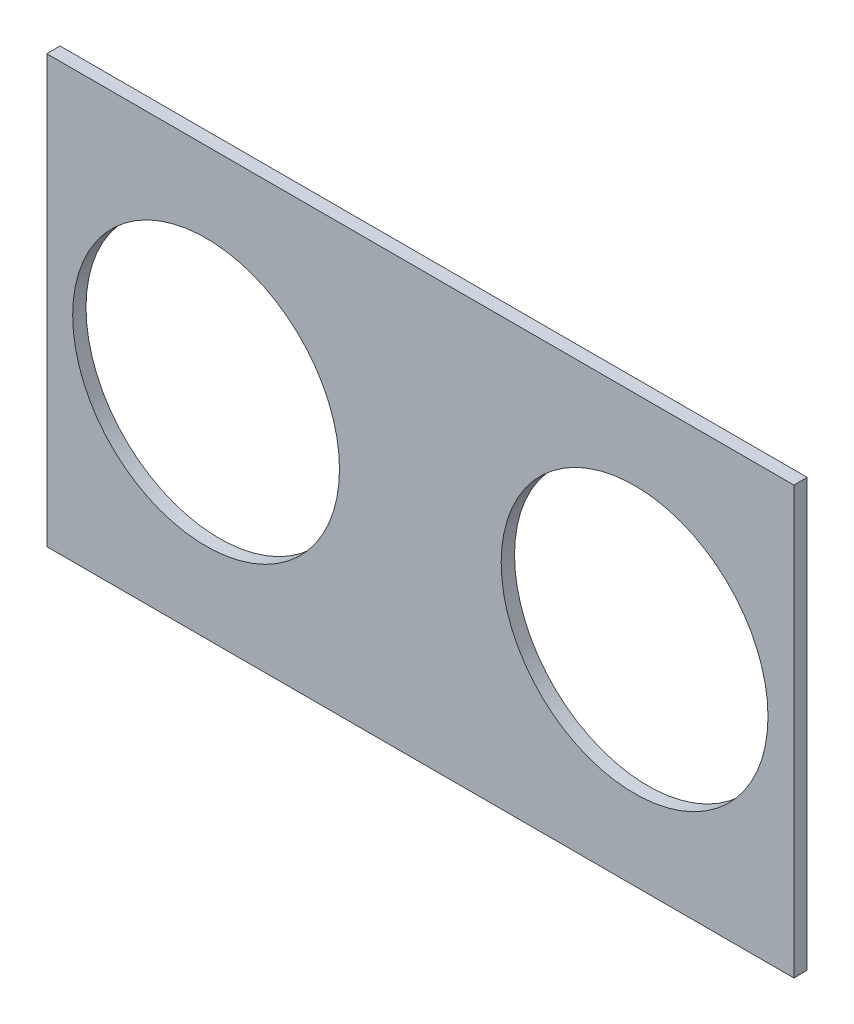
SolidWorks part; units mm, degrees
material "ABS PC"
ref_plane "Front Plane" through (0, 0, 0) normal (0, 0, 1) x (1, 0, 0)
ref_plane "Top Plane" through (0, 0, 0) normal (0, 1, 0) x (1, 0, 0)
ref_plane "Right Plane" through (0, 0, 0) normal (1, 0, 0) x (0, 0, -1)
sketch "Sketch1" plane through (0, 0, 0) normal (0, 0, 1) x (1, 0, 0)
  line L1 (-18.9548, 25.4) -> (69.9452, 25.4)
  line L2 (-18.9548, 25.4) -> (-18.9547, -25.4)
  line L3 (-18.9547, -25.4) -> (69.9452, -25.4)
  line L4 (69.9452, 25.4) -> (69.9452, -25.4)
  circle A0 centre (0, 0) radius 15.875
  circle A1 centre (50.9905, 0) radius 15.875
  circle A2 centre (0, 0) radius 15.875 construction
  circle A3 centre (50.9905, 0) radius 15.875 construction
extrude "Boss-Extrude1" add sketch "Sketch1" along normal up to surface (1.5875 mm away)
